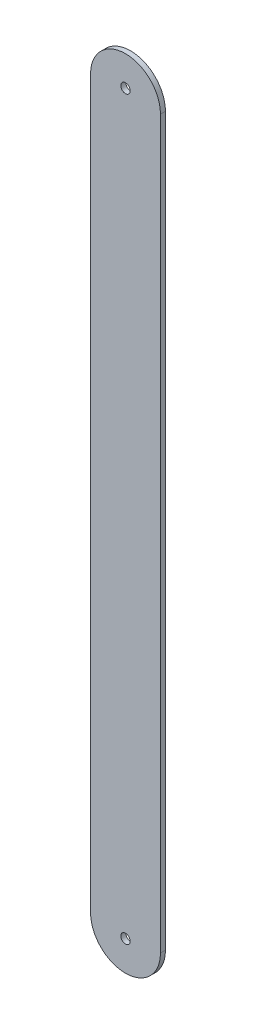
SolidWorks part; units mm, degrees
material "Thornel Mat VMA"
ref_plane "Front Plane" through (0, 0, 0) normal (0, 0, 1) x (1, 0, 0)
ref_plane "Top Plane" through (0, 0, 0) normal (0, 1, 0) x (1, 0, 0)
ref_plane "Right Plane" through (0, 0, 0) normal (1, 0, 0) x (0, 0, -1)
sketch "Sketch1" plane through (0, 0, 0) normal (0, 0, 1) x (1, 0, 0)
  line L0 (0, 115.5186) -> (0, -115.5186) construction
  line L1 (-11.1125, 115.5186) -> (11.1125, 115.5186)
  line L2 (-11.1125, 115.5186) -> (-11.1125, -115.5186)
  line L3 (-11.1125, -115.5186) -> (11.1125, -115.5186)
  line L4 (11.1125, 115.5186) -> (11.1125, -115.5186)
  arc A0 (-11.1125, 115.5186) -> (11.1125, 115.5186) centre (0, 115.5186) cw
  arc A1 (-11.1125, -115.5186) -> (11.1125, -115.5186) centre (0, -115.5186) ccw
  circle A2 centre (0, -117.1061) radius 1.5
  circle A3 centre (0, 117.1061) radius 1.5
  point P10 (0, 126.6311)
  point P11 (0, -126.6311)
  point P12 (11.1125, -116.2685)
  point P14 (0, 0)
  dimension "D2" = 253.2621
  dimension "D5" = 3
  dimension "D6" = 3
  dimension "D1" = 22.225
  dimension "D3" = 9.525
  dimension "D4" = 9.525
extrude "Boss-Extrude1" add sketch "Sketch1" along normal blind 1.5875 contours A0 L1 A3 | L1 L0 L3 L4 | L0 L1 L2 L3 | L3 A1 A2 region at (5.5562, 0, 0) region at (-5.5563, 0, 0) region at (0, 120.3532, 0) region at (0, -120.3532, 0)
